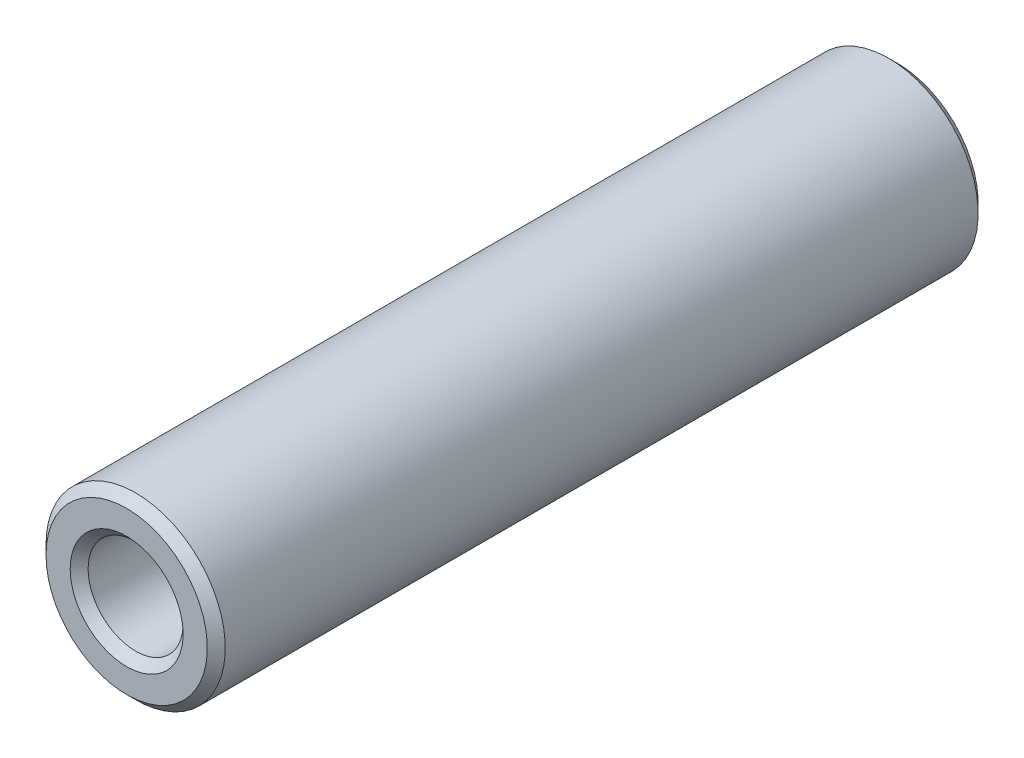
SolidWorks part; units mm, degrees
ref_plane "Front Plane" through (0, 0, 0) normal (0, 0, 1) x (1, 0, 0)
ref_plane "Top Plane" through (0, 0, 0) normal (0, 1, 0) x (1, 0, 0)
ref_plane "Right Plane" through (0, 0, 0) normal (1, 0, 0) x (0, 0, -1)
sketch "Sketch1" plane through (0, 0, 0) normal (0, 0, 1) x (1, 0, 0)
  line L0 (-1.5492, 2.15) -> (1.5492, 2.15)
  arc A0 (-1.5492, 2.15) -> (1.5492, 2.15) centre (0, 0) ccw
  point P3 (0, 2.65)
  dimension "D1" = 5.3
  dimension "D2" = 0.5
extrude "Extrude-Thin1" add sketch "Sketch1" along normal blind 6 thin thin type one direction wall 1
sketch "Sketch2" plane through (0, 0, 0) normal (0, 0, -1) x (-1, 0, 0)
  circle A0 centre (0, 0) radius 2.65
  circle A1 centre (0, 0) radius 5.65
  dimension "D1" = 5.3
  dimension "D2" = 3
extrude "Boss-Extrude1" add sketch "Sketch2" against normal blind 13
sketch "Sketch3" plane through (0, 0, 0) normal (0, 0, -1) x (-1, 0, 0)
  circle A2 centre (0, 0) radius 5.65 construction
  circle A3 centre (0, 0) radius 5.65
extrude "Boss-Extrude2" add sketch "Sketch3" along normal blind 30
chamfer "Chamfer1" distance 0.5 angle 45 1 edges at (-2.65, 0, 13)
chamfer "Chamfer2" distance 0.5 angle 45 1 edges at (-5.65, 0, 13)
sketch3d "3DSketch1"
  line L0 (0, 0, 0) -> (0, 0, 16.1968)
sketch "Sketch4" plane through (0, 0, -30) normal (0, 0, -1) x (-1, 0, 0)
  circle A0 centre (0, 0) radius 2.65
  dimension "D1" = 5.3
extrude "Cut-Extrude1" cut sketch "Sketch4" against normal blind 9
sketch "Sketch5" plane through (0, 0, -21) normal (0, 0, -1) x (-1, 0, 0)
  line L0 (-1.5492, 2.15) -> (1.5492, 2.15)
  circle A0 centre (0, 0) radius 2.65 construction
  circle A1 centre (0, 0) radius 2.65
  point P3 (0, 2.65)
  circle M2 centre (0, 0) radius 2.65
  dimension "D1" = 0.5
extrude "Cut-Extrude2" cut sketch "Sketch5" against normal blind 6 contours L0 M2 region at (0, -0.118, -21)
chamfer "Chamfer3" distance 0.5 angle 45 2 edges at (-5.65, 0, -30) (-2.65, 0, -30)
sketch "Sketch8" plane through (0, 0, 13) normal (0, 0, 1) x (1, 0, 0)
  circle A0 centre (0, 0) radius 5
  dimension "D1" = 10
extrude "Cut-Extrude5" cut sketch "Sketch8" against normal through all flip side to cut
chamfer "Chamfer4" distance 0.5 angle 45 2 edges at (5, 0, -30) (5, 0, 13)
